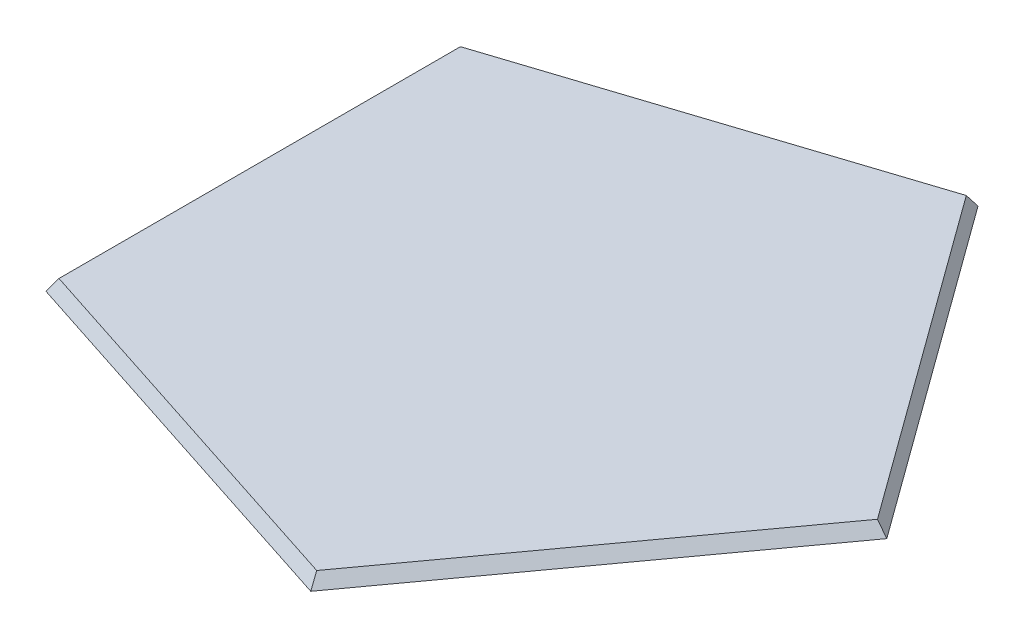
SolidWorks part; units mm, degrees
ref_plane "Front Plane" through (0, 0, 0) normal (0, 0, 1) x (1, 0, 0)
ref_plane "Top Plane" through (0, 0, 0) normal (0, 1, 0) x (1, 0, 0)
ref_plane "Right Plane" through (0, 0, 0) normal (1, 0, 0) x (0, 0, -1)
sketch "Sketch1" plane through (0, 0, 0) normal (0, 1, 0) x (1, 0, 0)
  line L1 (86.5248, 0) -> (26.7376, 82.2899)
  line L2 (26.7376, 82.2899) -> (-70, 50.858)
  line L3 (-70, 50.858) -> (-70, -50.858)
  line L4 (-70, -50.858) -> (26.7376, -82.2899)
  line L5 (26.7376, -82.2899) -> (86.5248, 0)
  circle A0 centre (0, 0) radius 70 construction
extrude "Boss-Extrude1" add sketch "Sketch1" along normal blind 3 contours L5 L1 L2 L3 L4
chamfer "Chamfer1" distance 3 angle 31.715 5 edges at (-70, 3, 0) (-21.6312, 3, -66.574) (56.6312, 3, -41.145) (56.6312, 3, 41.145) (-21.6312, 3, 66.574) first distance on face at (-70, 1.5, 0) first distance on face at (-21.6312, 1.5, -66.574) first distance on face at (56.6312, 1.5, -41.145) first distance on face at (56.6312, 1.5, 41.145) first distance on face at (-21.6312, 1.5, 66.574)
